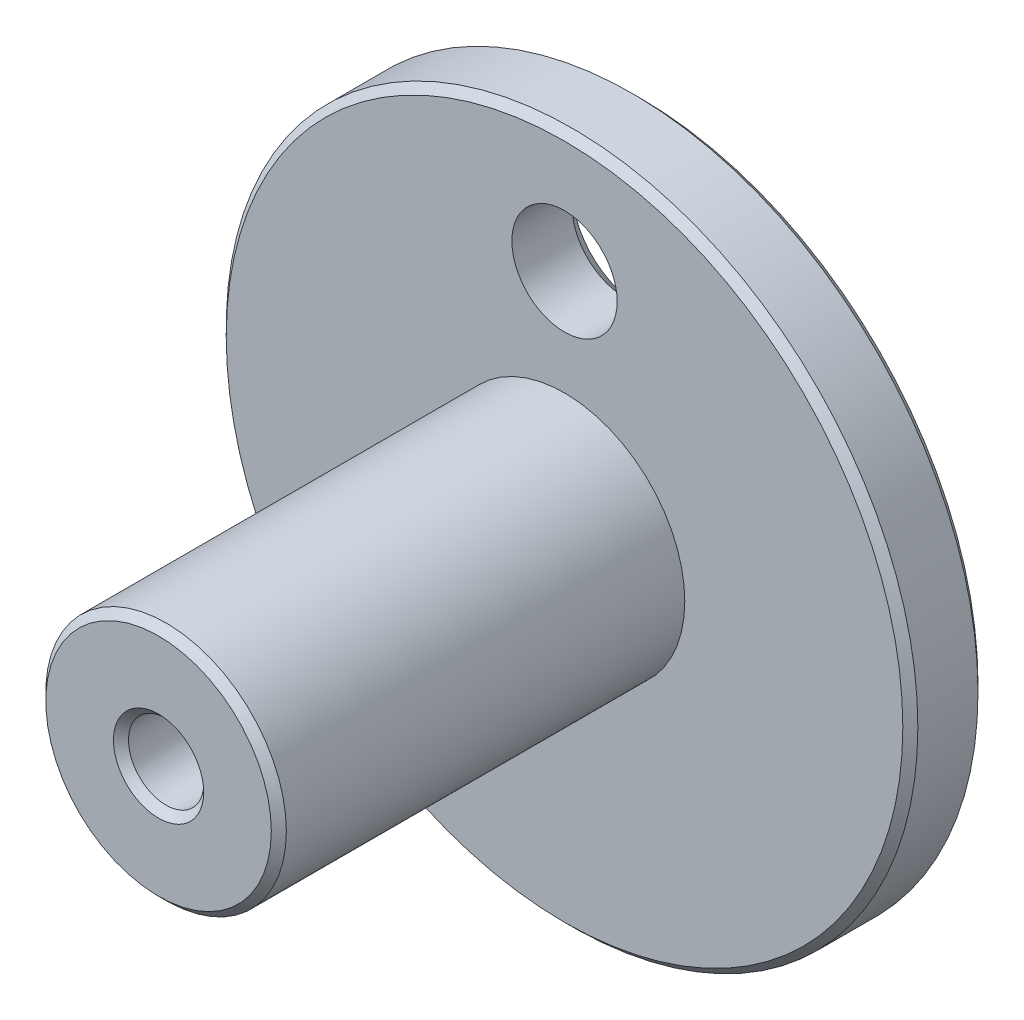
SolidWorks part; units mm, degrees
ref_plane "Front Plane" through (0, 0, 0) normal (0, 0, 1) x (1, 0, 0)
ref_plane "Top Plane" through (0, 0, 0) normal (0, 1, 0) x (1, 0, 0)
ref_plane "Right Plane" through (0, 0, 0) normal (1, 0, 0) x (0, 0, -1)
sketch "Sketch1" plane through (0, 0, 0) normal (0, 0, 1) x (1, 0, 0)
  circle A0 centre (0, 0) radius 23
  circle A1 centre (0, 0) radius 8
  circle A2 centre (0, 0) radius 15 construction
  circle A3 centre (0, 15) radius 3.5
  dimension "D1" = 46
  dimension "D2" = 16
  dimension "D3" = 30
  dimension "D4" = 7
extrude "Boss-Extrude1" add sketch "Sketch1" along normal blind 5
extrude "Boss-Extrude2" add sketch "Sketch1<3>" along normal blind 32 contours A1 region at (0, 0, 0)
sketch "Sketch1<3>" plane through (0, 0, 0) normal (0, 0, 1) x (1, 0, 0) same geometry as "Sketch1"
sketch "Sketch2" plane through (0, 0, 32) normal (0, 0, 1) x (1, 0, 0)
  circle A0 centre (0, 0) radius 2.5
  dimension "D1" = 5
extrude "Cut-Extrude1" cut sketch "Sketch2" against normal blind 37
chamfer "Chamfer2" distance 0.5 angle 45 4 edges at (8, 0, 32) (2.5, 0, 32) (23, 0, 0) (23, 0, 5)
hole_wizard "CSK for M6 Countersunk Flat Head Screw2" positions "Sketch5" profile "Sketch6" countersink size "M6" standard "ISO"
sketch "Sketch5" plane through (0, 0, 0) normal (0, 0, -1) x (-1, 0, 0)
  point P0 (0, 15)
sketch "Sketch6" plane through (0, 15, 0) normal (1, 0, 0) x (0, 1, 0)
  line L0 (0, 0) -> (0, 7.103)
  line L1 (0, 7.103) -> (3.5, 5)
  line L2 (3.5, 5) -> (3.5, 1)
  line L3 (3.5, 1) -> (4.5, 0)
  line L5 (4.5, 0) -> (0, 0)
  line L6 (-3.5, 1) -> (-4.5, 0) construction
  line L10 (0, 7.103) -> (-3.5, 5) construction
  line L11 (0, -6.35) -> (0, 107.95) construction
  dimension "Hole Dia." = 7
  dimension "Hole Depth" = 5
  dimension "Near C'Sink Dia." = 9
  dimension "Near C'Sink Angle" = 90
  dimension "Drill Angle" = 118
